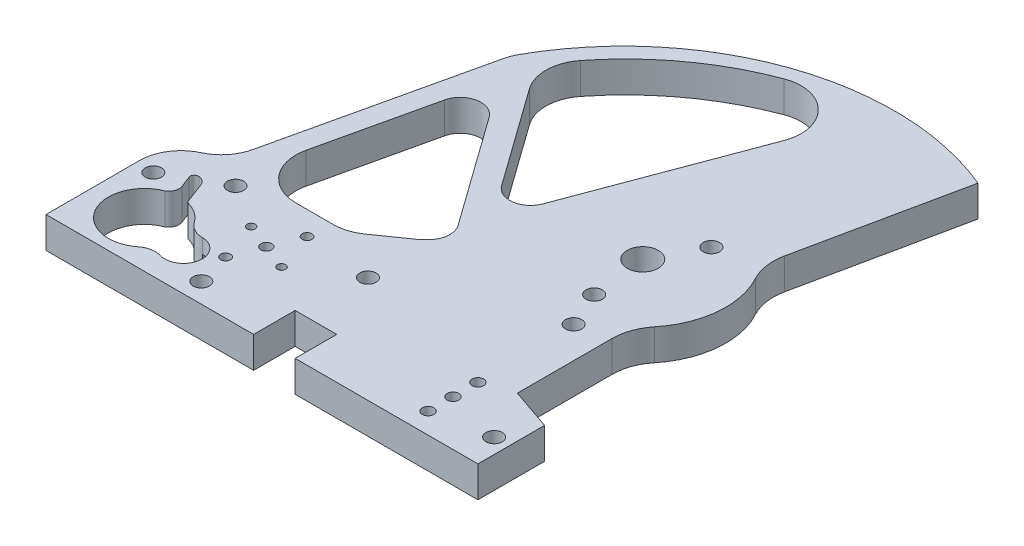
SolidWorks part; units mm, degrees
material "PE High Density"
ref_plane "Front Plane" through (0, 0, 0) normal (0, 0, 1) x (1, 0, 0)
ref_plane "Top Plane" through (0, 0, 0) normal (0, 1, 0) x (1, 0, 0)
ref_plane "Right Plane" through (0, 0, 0) normal (1, 0, 0) x (0, 0, -1)
other "Bounding Box"
ref_plane "Default Plane" through (-8.9266, -12.7485, 0) normal (-0.1736, 0.9848, 0) x (0.9848, 0.1736, 0)
sketch "Sketch1" plane through (0, 0, 0) normal (0, 1, 0) x (1, 0, 0)
  line L0 (-19.2303, 19.05) -> (-2.5851, 30.7051)
  line L1 (-69.85, 19.05) -> (69.85, 19.05)
  line L2 (-69.85, 19.05) -> (-69.85, -19.05)
  line L3 (-69.85, -19.05) -> (69.85, -19.05)
  line L4 (69.85, 19.05) -> (69.85, -19.05)
  line L5 (-69.85, 19.05) -> (69.85, -19.05) construction
  line L6 (-69.85, -19.05) -> (69.85, 19.05) construction
  line L7 (-2.5851, 30.7051) -> (0.7868, 49.8283)
  line L8 (0.7868, 49.8283) -> (13.0319, 64.4214)
  line L9 (45.7626, 67.3847) -> (65.8767, 19.05)
  line L10 (47.1268, 73.5864) -> (45.7626, 67.3847)
  circle A0 centre (33.2658, 57.15) radius 4.7625
  arc A1 (13.0319, 64.4214) -> (47.1268, 73.5864) centre (33.2658, 57.15) cw
  circle A2 centre (33.2658, 57.15) radius 76.2 construction
  point P0 (0, 0)
  dimension "D3" = 9.525
  dimension "D11" = 21.5008
  dimension "D17" = 152.4
  dimension "D6" = 38.1
  dimension "D8" = 36.5842
  dimension "D1" = 38.1
  dimension "D2" = 139.7
  dimension "D4" = 20.32
  dimension "D5" = 52.3528
  dimension "D7" = 6.35
  dimension "D9" = 19.05
  dimension "D10" = 19.4182
  dimension "D12" = 145
  dimension "D13" = 35
  dimension "D14" = 135
  dimension "D15" = 150
  dimension "D16" = 3.9733
extrude "Boss-Extrude1" add sketch "Sketch1" along normal blind 9.525 contours A1 L8 L7 L0 L1 L10 A0 | L4 L1 L2 L3 region at (0, 0, 0) region at (27.8967, 0, -42.5426)
sketch "Sketch2" plane through (0, 9.525, 0) normal (0, 1, 0) x (1, 0, 0)
  circle A0 centre (33.2658, 57.15) radius 76.2 construction
  dimension "D1" = 152.4
sketch "Sketch5" plane through (0, 9.525, 0) normal (0, 1, 0) x (1, 0, 0)
  line L0 (45.7626, 67.3847) -> (65.8767, 19.05) construction
  line L1 (69.85, -19.05) -> (49.53, -19.05)
  line L2 (69.85, -19.05) -> (69.85, 58.3315)
  line L3 (69.85, 58.3315) -> (49.53, 58.3315)
  line L4 (49.53, -19.05) -> (49.53, 58.3315)
  dimension "D1" = 20.32
extrude "Cut-Extrude4" cut sketch "Sketch5" against normal through all both and the other way through all
fillet "Fillet9" radius 12.7 1 edges at (-69.85, 4.7625, -19.05)
sketch "Sketch6" plane through (0, 9.525, 0) normal (0, 1, 0) x (1, 0, 0)
  line L1 (-57.15, 19.05) -> (-40.8203, 90.7577)
  line L2 (0.7868, 49.8283) -> (31.4279, 131.6561)
  line L3 (-50.6374, 19.05) -> (-36.1123, 82.8336)
  line L4 (-57.15, 19.05) -> (-19.2303, 19.05) construction
  line L5 (13.0319, 64.4214) -> (38.7682, 133.1511)
  line L6 (46.378, 65.9058) -> (58.1051, 122.2514)
  line L7 (-1.8369, 34.9484) -> (-0.1716, 44.3925)
  line L8 (45.7626, 67.3847) -> (49.53, 58.3315) construction
  line L9 (-57.15, 19.05) -> (-50.6374, 19.05)
  line L10 (0.7868, 49.8283) -> (13.0319, 64.4214)
  line L13 (-1.8369, 34.9484) -> (-36.1123, 82.8336)
  line L14 (-2.5851, 30.7051) -> (0.7868, 49.8283) construction
  line L15 (-1.8369, 34.9484) -> (0.7868, 49.8283)
  line L16 (-34.4703, 92.3103) -> (-0.1716, 44.3925)
  line L17 (-0.1716, 44.3925) -> (-1.8369, 34.9484)
  line L18 (46.378, 65.9058) -> (49.53, 58.3315)
  line L19 (49.53, 58.3315) -> (64.3361, 128.6003)
  circle A2 centre (33.2658, 57.15) radius 76.2 construction
  arc A4 (-40.8203, 90.7577) -> (64.3361, 128.6003) centre (32.4597, 52.1531) cw
  arc A5 (38.7682, 133.1511) -> (58.1051, 122.2514) centre (37.5674, 108.4182) cw
  arc A6 (-34.4703, 92.3103) -> (31.4279, 131.6561) centre (35.9864, 49.1637) cw
  line M10 (-19.2303, 19.05) -> (-57.15, 19.05)
  line M15 (49.53, 58.3315) -> (45.7626, 67.3847)
  line M18 (13.0319, 64.4214) -> (0.7868, 49.8283)
  dimension "D8" = 71.7077
  dimension "D12" = 82.6183
  dimension "D5" = 6.35
  dimension "D6" = 6.35
  dimension "D7" = 58.928
  dimension "D10" = 6.35
  dimension "D11" = 54.406
  dimension "D13" = 58.888
extrude "Boss-Extrude4" add sketch "Sketch6" against normal up to surface (9.525 mm away) contours L5 A5 L6 L1 L3 L13 L15 L16 L2 M15 M10 M18 region at (-47.3478, 9.525, -54.531) up to face at (-1.6293, 0, -32.9225)
sketch "Sketch4" plane through (0, 0, 0) normal (0, -1, 0) x (-1, 0, 0)
  line L1 (69.85, 6.35) -> (69.85, -19.05) construction
  line L5 (69.85, -19.05) -> (-49.53, -19.05) construction
  circle A0 centre (53.975, -8.0518) radius 10.9728
  dimension "D1" = 21.9456
  dimension "D2" = 15.875
  dimension "D3" = 10.9982
extrude "Cut-Extrude3" cut sketch "Sketch4" against normal through all both and the other way through all
fillet "Fillet13" radius 12.7 13 edges at (-57.15, 4.7625, -19.05) (-50.6374, 4.7625, -19.05) (-19.2303, 4.7625, -19.05) (-2.5851, 4.7625, -30.7051) (-0.1716, 4.7625, -44.3925) (-34.4703, 4.7625, -92.3103) (31.4279, 4.7625, -131.6561) (38.7682, 4.7625, -133.1511) (58.1051, 4.7625, -122.2514) (47.1268, 4.7625, -73.5864) (46.378, 4.7625, -65.9058) (-40.8203, 4.7625, -90.7577) (49.53, 4.7625, -58.3315)
fillet "Fillet14" radius 6.35 5 edges at (0.7868, 4.7625, -49.8283) (-1.8369, 4.7625, -34.9484) (-36.1123, 4.7625, -82.8336) (13.2325, 4.7625, -64.9569) (45.7626, 4.7625, -67.3847)
sketch "Sketch7" plane through (0, 0, 0) normal (0, -1, 0) x (-1, 0, 0)
  line L0 (69.85, -19.05) -> (-49.53, -19.05) construction
  line L1 (3.81, -19.05) -> (16.51, -19.05)
  line L2 (3.81, -19.05) -> (3.81, -12.7)
  line L3 (3.81, -12.7) -> (16.51, -12.7)
  line L4 (16.51, -19.05) -> (16.51, -12.7)
  line L5 (-49.53, 57.0081) -> (-49.53, -19.05) construction
  dimension "D1" = 53.34
  dimension "D2" = 12.7
  dimension "D3" = 6.35
extrude "Cut-Extrude5" cut sketch "Sketch7" against normal through all both and the other way through all
fillet "Fillet15" radius 1.27 1 edges at (-3.81, 4.7625, 19.05)
sketch "Sketch8" plane through (0, 9.525, 0) normal (0, 1, 0) x (1, 0, 0)
  line L1 (-69.85, -19.05) -> (-10.16, -19.05)
  line L2 (-69.85, -19.05) -> (-69.85, -22.225)
  line L3 (-69.85, -22.225) -> (-10.16, -22.225)
  line L4 (-10.16, -19.05) -> (-10.16, -22.225)
  line L5 (-2.54, -19.05) -> (49.53, -19.05) construction
  line L6 (2.54, -19.05) -> (15.24, -19.05)
  line L7 (2.54, -19.05) -> (2.54, -22.225)
  line L8 (2.54, -22.225) -> (15.24, -22.225)
  line L9 (15.24, -19.05) -> (15.24, -22.225)
  line L10 (-3.81, -12.7) -> (-3.81, -17.78) construction
  dimension "D1" = 3.175
  dimension "D2" = 59.69
  dimension "D3" = 12.7
  dimension "D4" = 6.35
  dimension "D5" = 3.175
extrude "Boss-Extrude5" add sketch "Sketch8" against normal up to surface (9.525 mm away) up to face at (-53.975, 0, 19.0246)
sketch "Sketch9" plane through (0, 0, 0) normal (0, -1, 0) x (1, 0, 0)
  line L1 (-27.6157, -2.921) -> (33.2658, -57.15) construction
  line L2 (-10.16, 22.225) -> (-69.85, 22.225) construction
  circle A0 centre (-27.6157, -2.921) radius 14.2875
  dimension "D1" = 28.575
  dimension "D2" = 81.5312
  dimension "D3" = 25.146
extrude "Cut-Extrude6" cut sketch "Sketch9" against normal blind 5.08
sketch "Sketch10" plane through (0, 5.08, 0) normal (0, -1, 0) x (-1, 0, 0)
  circle A1 centre (27.6157, 2.921) radius 1.651
  dimension "D1" = 3.302
extrude "Cut-Extrude7" cut sketch "Sketch10" against normal through all both and the other way through all
sketch "Sketch11" plane through (0, 9.525, 0) normal (0, 1, 0) x (1, 0, 0)
  line L0 (52.7216, 73.4788) -> (49.8029, 59.6266)
  line L1 (49.8029, 59.6266) -> (64.3361, 128.6003) construction
  line L2 (49.53, 57.0081) -> (49.53, 37.6401)
  line L3 (49.53, 57.0081) -> (49.53, -19.05) construction
  circle A0 centre (33.2658, 57.15) radius 25.4
  arc A2 (49.8029, 59.6266) -> (49.53, 57.0081) centre (62.23, 57.0081) ccw
  line M10 (49.53, -19.05) -> (49.53, 57.0081)
  arc M11 (49.53, 57.0081) -> (49.8029, 59.6266) centre (62.23, 57.0081) cw
  line M12 (49.8029, 59.6266) -> (64.3361, 128.6003)
  dimension "D1" = 50.8
extrude "Boss-Extrude6" add sketch "Sketch11" against normal up to surface (9.525 mm away) contours A0 M10 M12 M11 region at (53.6069, 9.525, -55.4705) up to face at (-27.6157, 0, -17.2085)
fillet "Fillet16" radius 15.24 2 edges at (49.53, 4.7625, -37.6401) (52.7216, 4.7625, -73.4788)
sketch "Sketch12" plane through (0, 5.08, 0) normal (0, -1, 0) x (1, 0, 0)
  line L3 (-19.942, -19.4842) -> (-19.942, 22.225) construction
  line L5 (-10.16, 22.225) -> (-69.85, 22.225) construction
  circle A0 centre (-27.6157, -2.921) radius 1.651 construction
  circle A1 centre (-35.2893, -5.9505) radius 1.25
  circle A2 centre (-31.1409, 6.0083) radius 1.5
  circle A3 centre (-19.942, 0.1085) radius 1.25
  circle A4 centre (-24.0904, -11.8503) radius 1.5
  arc A5 (-15.9502, -21.3468) -> (-23.2346, -19.05) centre (-23.2346, -31.75) ccw construction
  circle B0 centre (-24.0904, -11.8503) radius 1.5
  circle B1 centre (-35.2893, -5.9505) radius 1.25
  circle B2 centre (-31.1409, 6.0083) radius 1.5
  circle B3 centre (-19.942, 0.1085) radius 1.25
  circle B4 centre (-27.6157, -2.921) radius 4
  circle B5 centre (-27.6157, -2.921) radius 13.925
sketch_block_instance "Wepon motor-1"
sketch_block "Wepon motor" parameters "D1"=27.85, "D2"=3, "D3"=2.5, "D4"=8
extrude "Cut-Extrude8" cut sketch "Sketch12" against normal up to surface (4.445 mm away) contours A4 | A1 | A2 | B3 | A3 | A3 region at (-35.2893, 5.08, -5.9505) region at (-31.1409, 5.08, 6.0083) region at (-19.942, 5.08, 0.1085) region at (-24.0904, 5.08, -11.8503) up to face at (-2.0065, 9.525, -15.4705)
sketch "Sketch13" plane through (0, 0, 0) normal (0, -1, 0) x (-1, 0, 0)
  line L0 (10.16, -22.225) -> (69.85, -22.225) construction
  line L1 (69.85, 6.35) -> (69.85, -22.225) construction
  line L2 (51.6741, 3.1427) -> (53.9746, 9.2296)
  line L3 (57.857, 9.5431) -> (56.5388, 6.0555)
  line L4 (50.856, 2.3768) -> (58.2843, 2.0037)
  circle A2 centre (28.3994, -16.1925) radius 2.4892
  circle A3 centre (41.1691, 1.9672) radius 2.4892
  circle A4 centre (64.5668, 5.3086) radius 2.4892
  arc A7 (39.9498, -4.4075) -> (41.5187, -15.6078) centre (39.915, -10.1224) ccw
  arc A8 (39.915, -4.4074) -> (45.1206, -1.7461) centre (39.9518, 1.9426) ccw
  arc A9 (41.5187, -15.6078) -> (47.2419, -16.7237) centre (43.3006, -21.7026) cw
  circle A11 centre (39.915, -10.1224) radius 5.715
  arc A12 (39.915, -4.4074) -> (44.5381, -2.4494) centre (39.9518, 1.9426) ccw
  arc A13 (41.5187, -15.6078) -> (46.487, -16.2099) centre (43.3006, -21.7026) cw
  arc A14 (50.856, 2.3768) -> (51.6741, 3.1427) centre (50.4861, 3.5917) ccw
  arc A15 (53.9746, 9.2296) -> (56.4853, 11.2488) centre (56.9445, 8.1072) cw
  arc A16 (56.4853, 11.2488) -> (57.857, 9.5431) centre (56.669, 9.9921) cw
  arc A17 (56.5388, 6.0555) -> (58.2843, 2.0037) centre (59.5088, 4.933) ccw
  line B0 (51.6741, 3.1427) -> (53.9746, 9.2296)
  line B1 (56.5388, 6.0555) -> (57.857, 9.5431)
  line B2 (59.1668, 11.9371) -> (56.2623, 14.2113)
  line B3 (54.2914, 13.6603) -> (53.2994, 11.0355)
  circle B4 centre (28.3994, -16.1925) radius 4.7625
  circle B5 centre (41.1691, 1.9672) radius 4.7625
  circle B6 centre (64.5668, 5.3086) radius 4.7625
  arc B7 (47.2419, -16.7237) -> (58.2843, 2.0037) centre (54.0523, -8.1202) ccw
  arc B8 (39.9325, -4.4074) -> (41.5187, -15.6078) centre (39.915, -10.1224) ccw
  arc B9 (47.2419, -16.7237) -> (41.5187, -15.6078) centre (43.3006, -21.7026) ccw
  arc B10 (45.1206, -1.7461) -> (39.9325, -4.4074) centre (39.9519, 1.9426) cw
  arc B11 (50.856, 2.3768) -> (51.6741, 3.1427) centre (50.4861, 3.5917) ccw
  arc B12 (56.5388, 6.0555) -> (58.2843, 2.0037) centre (59.5088, 4.933) ccw
  arc B13 (53.9746, 9.2296) -> (56.4853, 11.2488) centre (56.9445, 8.1072) cw
  arc B14 (56.4853, 11.2488) -> (57.857, 9.5431) centre (56.669, 9.9921) cw
  arc B15 (50.856, 2.3768) -> (45.1206, -1.7461) centre (54.0523, -8.1202) ccw
  arc B16 (26.9014, -10.349) -> (33.1492, -19.9115) centre (28.3994, -16.1925) ccw
  arc B17 (33.1492, -19.9115) -> (37.2652, -17.8006) centre (37.1178, -22.5816) cw
  arc B18 (37.2652, -17.8006) -> (41.9338, -17.0647) centre (37.6565, -5.1066) ccw
  arc B19 (41.9338, -17.0647) -> (47.18, -18.4806) centre (43.5377, -21.549) cw
  arc B20 (49.0637, -20.2979) -> (47.18, -18.4806) centre (56.8928, -10.2982) cw
  arc B21 (49.0637, -20.2979) -> (64.2612, -17.915) centre (55.097, -9.1225) ccw
  arc B22 (64.2612, -17.915) -> (66.7679, -1.9177) centre (54.0523, -8.1202) ccw
  arc B23 (66.7679, -1.9177) -> (68.5811, 1.6191) centre (56.5124, 5.5732) ccw
  arc B24 (68.5811, 1.6191) -> (68.9549, 2.3892) centre (71.5983, 0.6305) cw
  arc B25 (68.9549, 2.3892) -> (61.6247, 9.6815) centre (64.5668, 5.3086) ccw
  arc B26 (61.6247, 9.6815) -> (59.6498, 10.8362) centre (60.9158, 10.7352) cw
  arc B27 (59.6498, 10.8362) -> (59.1668, 11.9371) centre (58.3838, 10.9372) ccw
  arc B28 (56.2623, 14.2113) -> (54.2914, 13.6603) centre (55.4794, 13.2113) ccw
  arc B29 (53.2994, 11.0355) -> (51.0076, 9.0562) centre (50.3294, 12.158) cw
  arc B30 (51.0076, 9.0562) -> (45.8856, 7.0672) centre (54.8054, -8.3134) ccw
  arc B31 (45.8856, 7.0672) -> (43.1184, 6.8639) centre (44.2927, 9.8138) cw
  arc B32 (43.1184, 6.8639) -> (36.0999, 0.5245) centre (41.1691, 1.9672) ccw
  arc B33 (36.0999, 0.5245) -> (34.7175, -5.456) centre (29.9924, -1.2137) cw
  arc B34 (26.9014, -10.349) -> (30.8214, -8.5944) centre (23.7477, 1.9532) ccw
  arc B35 (30.8214, -8.5944) -> (34.7175, -5.456) centre (14.8524, 15.217) ccw
  dimension "D3" = 4.9784
  dimension "D1" = 27.5336
  dimension "D2" = 5.2832
sketch_block_instance "Wire cover-1"
sketch_block "Wire cover"
extrude "Cut-Extrude10" cut sketch "Sketch13" against normal through all both and the other way through all contours L4 A17 L3 A16 A15 L2 A14 | A4 | A11 | A2
fillet "Fillet18" radius 6.35 2 edges at (-43.299, 4.7625, 5.517) (-44.483, 4.7625, 13.5567)
sketch "Sketch14" plane through (0, 0, 0) normal (0, -1, 0) x (-1, 0, 0)
  line B0 (-64.3361, 128.6003) -> (-54.0401, 79.736)
  line B1 (-49.53, 31.4772) -> (-49.53, -19.05)
  line B2 (-49.53, -19.05) -> (-15.24, -19.05)
  line B3 (-15.24, -19.05) -> (-15.24, -22.225)
  line B4 (-15.24, -22.225) -> (-2.54, -22.225)
  line B5 (-2.54, -22.225) -> (-2.54, -19.05)
  line B6 (-2.54, -19.05) -> (2.54, -19.05)
  line B7 (3.81, -17.78) -> (3.81, -12.7)
  line B8 (3.81, -12.7) -> (16.51, -12.7)
  line B9 (16.51, -12.7) -> (16.51, -19.05)
  line B10 (16.51, -19.05) -> (10.16, -19.05)
  line B11 (10.16, -19.05) -> (10.16, -22.225)
  line B12 (10.16, -22.225) -> (69.85, -22.225)
  line B13 (69.85, -22.225) -> (69.85, 6.35)
  line B14 (55.4349, 26.5812) -> (41.206, 89.0639)
  arc B15 (-54.0401, 79.736) -> (-55.5701, 69.3024) centre (-68.9526, 76.5938) cw
  arc B16 (-55.5701, 69.3024) -> (-52.9559, 41.1045) centre (-33.2658, 57.15) ccw
  arc B17 (-52.9559, 41.1045) -> (-49.53, 31.4772) centre (-64.77, 31.4772) cw
  arc B18 (3.81, -17.78) -> (2.54, -19.05) centre (2.54, -17.78) cw
  arc B19 (39.9214, 92.4179) -> (-64.3361, 128.6003) centre (-32.4597, 52.1531) ccw
  arc B20 (39.9214, 92.4179) -> (41.206, 89.0639) centre (28.8231, 86.244) cw
  arc B21 (55.4349, 26.5812) -> (62.484, 17.8756) centre (67.8179, 29.4011) ccw
  arc B22 (62.484, 17.8756) -> (69.85, 6.35) centre (57.15, 6.35) cw
sketch_block_instance "Block1-1"
sketch_block "Block1"
sketch "Sketch15" plane through (0, 9.525, 0) normal (0, 1, 0) x (1, 0, 0)
  line L2 (15.24, -19.05) -> (49.53, -19.05) construction
  line L3 (-69.85, 6.35) -> (-69.85, -22.225) construction
  circle A2 centre (40.5384, 70.866) radius 2.5
  circle A3 centre (35.179, 40.386) radius 2.5
  circle A4 centre (39.9034, 29.3624) radius 2.5
  dimension "D1" = 5
  dimension "D4" = 5
  dimension "D7" = 5
  dimension "D2" = 89.916
  dimension "D3" = 110.3884
  dimension "D5" = 59.436
  dimension "D6" = 105.029
  dimension "D8" = 48.4124
  dimension "D9" = 109.7534
extrude "Cut-Extrude11" cut sketch "Sketch15" against normal through all both and the other way through all
sketch "Sketch16" plane through (0, 9.525, 0) normal (0, 1, 0) x (1, 0, 0)
  line L0 (49.53, -12.7) -> (55.88, -6.35)
  line L1 (49.53, 31.4772) -> (49.53, -19.05) construction
  line L2 (55.88, -6.35) -> (55.88, -19.05)
  line L3 (55.88, -19.05) -> (49.53, -19.05)
  line L4 (49.53, -12.7) -> (49.53, -19.05)
  line L5 (55.88, -12.065) -> (53.6803, -10.795)
  line L6 (53.6803, -10.795) -> (53.6803, -17.145)
  line L7 (53.6803, -17.145) -> (55.88, -15.875)
  dimension "D1" = 6.35
  dimension "D2" = 6.35
  dimension "D3" = 12.7
  dimension "D4" = 3.175
  dimension "D5" = 3.81
  dimension "D6" = 6.35
  dimension "D7" = 2.54
  dimension "D8" = 2.54
extrude "Boss-Extrude7" add sketch "Sketch16" against normal up to surface (9.525 mm away) contours L7 L6 L5 L2 L0 L4 L3 region at (52.6882, 9.525, 14.1431) up to face at (40.5384, 0, -68.366)
sketch "Sketch18" plane through (0, 9.525, 0) normal (0, 1, 0) x (1, 0, 0)
  line B0 (49.53, -12.7) -> (49.53, -19.05)
  line B1 (49.53, -19.05) -> (55.88, -19.05)
  line B2 (55.88, -19.05) -> (55.88, -15.875)
  line B3 (55.88, -15.875) -> (53.6803, -17.145)
  line B4 (53.6803, -17.145) -> (53.6803, -10.795)
  line B5 (53.6803, -10.795) -> (55.88, -12.065)
  line B6 (55.88, -12.065) -> (55.88, -6.35)
  line B7 (55.88, -6.35) -> (49.53, -12.7)
sketch_block_instance "Block3-1"
sketch_block "Block3"
sketch "Sketch19" plane through (0, 9.525, 0) normal (0, 1, 0) x (-1, 0, 0)
  line L0 (69.85, -6.35) -> (69.85, 22.225) construction
  line L2 (69.85, 22.225) -> (10.16, 22.225) construction
  circle A0 centre (48.4632, -14.351) radius 2.4892
  circle A3 centre (3.9116, -10.287) radius 2.4892
  dimension "D1" = 4.9784
  dimension "D2" = 21.3868
  dimension "D3" = 36.576
  dimension "D4" = 32.512
  dimension "D5" = 65.9384
extrude "Cut-Extrude12" cut sketch "Sketch19" against normal through all both and the other way through all
sketch "Sketch20" plane through (0, 9.525, 0) normal (0, 1, 0) x (1, 0, 0)
  line L0 (56.7659, 115.8168) -> (49.4775, 80.7977)
  line L1 (34.3228, 121.2794) -> (21.3277, 86.5755)
  line L2 (28.6405, 78.1474) -> (32.968, 78.6487)
  arc A0 (53.3931, 127.3036) -> (56.7659, 115.8168) centre (44.3324, 118.4045) cw
  arc A1 (53.3931, 127.3036) -> (34.3228, 121.2794) centre (46.2163, 116.8258) ccw
  arc A3 (21.3277, 86.5755) -> (28.6405, 78.1474) centre (27.2744, 84.3487) ccw
  arc A4 (32.968, 78.6487) -> (39.8884, 76.711) centre (33.1439, 65.9499) cw
  arc A5 (39.8884, 76.711) -> (49.4775, 80.7977) centre (43.2607, 82.0916) ccw
  dimension "D1" = 12.7
extrude "Boss-Extrude8" add sketch "Sketch20" against normal up to surface (9.525 mm away) up to face at (-48.4632, 0, -11.8618)
sketch "Sketch22" plane through (0, 9.525, 0) normal (0, 1, 0) x (1, 0, 0)
  line L0 (49.53, 31.4772) -> (49.53, -12.7) construction
  line L1 (15.24, -19.05) -> (55.88, -19.05) construction
  line B0 (62.23, 2.5212) -> (49.53, -1.8375)
  line B1 (49.53, -1.8375) -> (49.53, -19.05)
  line B2 (49.53, -19.05) -> (62.23, -19.05)
  line B3 (62.23, -19.05) -> (62.23, 2.5212)
  circle B4 centre (54.1293, -12.6738) radius 2.4892
sketch_block_instance "Front-1"
sketch_block "Block4" parameters "D1"=4.9784
extrude "Boss-Extrude9" add sketch "Sketch22" against normal up to surface (9.525 mm away) up to face at (-48.4632, 0, -11.8618)
sketch "Sketch23" plane through (0, 9.525, 0) normal (0, 1, 0) x (1, 0, 0)
  circle A0 centre (54.1293, -12.6738) radius 2.4892
extrude "Cut-Extrude13" cut sketch "Sketch23" against normal through all both and the other way through all
sketch "Sketch24" plane through (0, 0, 0) normal (0, -1, 0) x (-1, 0, 0)
  line L0 (-15.24, -19.05) -> (-62.23, -19.05) construction
  line L1 (-62.23, 2.5212) -> (-62.23, -19.05) construction
  line L2 (-62.23, -1.8375) -> (-49.53, -1.8375)
  line L3 (-49.53, -1.8375) -> (-49.53, 2.5212)
  line L4 (-62.23, -1.8375) -> (-49.53, 2.5212)
  line L5 (-62.23, -1.8375) -> (-62.23, 2.5212)
  line L6 (-62.23, 2.5212) -> (-55.88, 0.3418)
  line L7 (-55.88, 0.3418) -> (-62.23, -1.8375)
  circle A0 centre (-57.6307, -12.6738) radius 2.4892
  point P12 (0, 0)
  line B0 (-49.53, 2.5212) -> (-62.23, -1.8375)
  line B1 (-62.23, -1.8375) -> (-62.23, -19.05)
  line B2 (-62.23, -19.05) -> (-49.53, -19.05)
  line B3 (-49.53, -19.05) -> (-49.53, 2.5212)
  circle B4 centre (-57.6307, -12.6738) radius 2.4892
sketch_block_instance "Block4-2"
extrude "Boss-Extrude10" add sketch "Sketch24" against normal up to surface (9.525 mm away) contours L4 L3 L2 up to face at (54.1293, 9.525, 15.163)
sketch "Sketch26" plane through (0, 0, 0) normal (0, -1, 0) x (-1, 0, 0)
  circle A0 centre (-54.1293, -12.6738) radius 2.4892
extrude "Boss-Extrude11" add sketch "Sketch26" against normal up to surface (9.525 mm away) up to face at (5.1611, 9.525, -13.8926)
sketch "Sketch25" plane through (0, 0, 0) normal (0, -1, 0) x (-1, 0, 0)
  line L5 (-62.23, -1.8375) -> (-55.88, 0.3418)
  line L6 (-62.23, -1.8375) -> (-49.53, 2.5212) construction
  line L7 (-55.88, 0.3418) -> (-62.23, 2.5212)
  line L8 (-62.23, 2.5212) -> (-62.23, -1.8375)
  circle A0 centre (-57.6307, -12.6738) radius 2.4892
extrude "Cut-Extrude14" cut sketch "Sketch25" against normal through all both and the other way through all
sketch "Sketch27" plane through (0, 9.525, 0) normal (0, 1, 0) x (1, 0, 0)
  line L0 (-16.51, -12.7) -> (-16.51, -19.05)
  line L1 (-16.51, -19.05) -> (-10.16, -19.05)
  line L2 (-10.16, -19.05) -> (-10.16, -22.225)
  line L3 (-10.16, -22.225) -> (2.54, -22.225)
  line L4 (2.54, -22.225) -> (2.54, -19.05)
  line L5 (2.54, -19.05) -> (-2.54, -19.05)
  line L6 (-16.51, -12.7) -> (-3.81, -12.7)
  line L7 (-3.81, -12.7) -> (-3.81, -17.78)
  line L8 (62.23, -19.05) -> (62.23, -1.8375) construction
  line L9 (15.24, -19.05) -> (62.23, -19.05)
  line L10 (15.24, -19.05) -> (15.24, -22.225)
  line L11 (15.24, -22.225) -> (62.23, -22.225)
  line L12 (62.23, -19.05) -> (62.23, -22.225)
  line L13 (2.54, -22.225) -> (15.24, -22.225) construction
  arc A0 (-3.81, -17.78) -> (-2.54, -19.05) centre (-2.54, -17.78) ccw
extrude "Boss-Extrude12" add sketch "Sketch27" against normal up to surface (9.525 mm away) up to face at (57.6307, 0, 15.163)
sketch "Sketch28" plane through (0, 9.525, 0) normal (0, 1, 0) x (1, 0, 0)
  line L0 (40.64, -22.225) -> (40.64, 155.575) construction
  line L1 (-69.85, -22.225) -> (62.23, -22.225) construction
  line L2 (62.23, -22.225) -> (62.23, -1.8375) construction
  circle A0 centre (40.64, -8.255) radius 1.778
  circle A1 centre (40.64, -15.875) radius 1.778
  circle A2 centre (40.64, -0.635) radius 1.778
  arc A4 (40.64, 8.763) -> (40.64, 5.207) centre (40.64, 6.985) ccw [skipped]
  dimension "D2" = 3.556
  dimension "D3" = 3.556
  dimension "D1" = 177.8
  dimension "D4" = 6.35
  dimension "D5" = 7.62
  dimension "D7" = 21.59
  dimension "D6" = 3
extrude "Cut-Extrude15" cut sketch "Sketch28" against normal through all both and the other way through all
sketch "Sketch29" plane through (0, 9.525, 0) normal (0, 1, 0) x (1, 0, 0)
  line L0 (-69.85, -22.225) -> (62.23, -22.225) construction
  line L1 (-6.35, -22.225) -> (6.35, -22.225)
  line L2 (-6.35, -22.225) -> (-6.35, -9.525)
  line L3 (-6.35, -9.525) -> (6.35, -9.525)
  line L4 (6.35, -22.225) -> (6.35, -9.525)
  line L5 (-69.85, 6.35) -> (-69.85, -22.225) construction
  dimension "D1" = 12.7
  dimension "D2" = 12.7
  dimension "D3" = 63.5
extrude "Cut-Extrude16" cut sketch "Sketch29" against normal through all both and the other way through all
